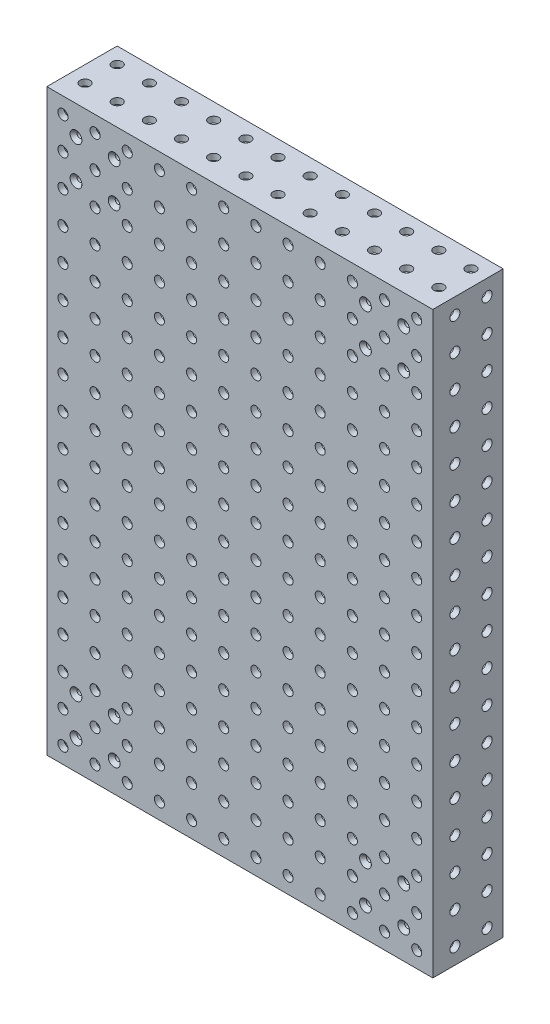
SolidWorks part; units mm, degrees
material "Malleable Cast Iron"
ref_plane "Front Plane" through (0, 0, 0) normal (0, 0, 1) x (1, 0, 0)
ref_plane "Top Plane" through (0, 0, 0) normal (0, 1, 0) x (1, 0, 0)
ref_plane "Right Plane" through (0, 0, 0) normal (1, 0, 0) x (0, 0, -1)
sketch "Sketch1" plane through (0, 0, 0) normal (0, 0, 1) x (1, 0, 0)
  line L0 (25.4, 25.4) -> (25.4, 0) construction
  line L1 (0, 0) -> (609.6, 0)
  line L2 (0, 0) -> (0, 914.4)
  line L3 (0, 914.4) -> (609.6, 914.4)
  line L4 (609.6, 0) -> (609.6, 914.4)
  line L5 (25.4, 0) -> (25.4, 25.4) construction
  line L6 (25.4, 25.4) -> (0, 25.4) construction
  line L7 (584.2, 889) -> (584.2, 914.4) construction
  line L8 (584.2, 889) -> (609.6, 889) construction
  line L9 (46.0375, 868.3625) -> (106.3625, 808.0375) construction
  line L10 (503.2375, 868.3625) -> (563.5625, 808.0375) construction
  line L11 (46.0375, 106.3625) -> (106.3625, 46.0375) construction
  line L12 (503.2375, 106.3625) -> (563.5625, 46.0375) construction
  circle A0 centre (25.4, 25.4) radius 7.9375
  circle A1 centre (76.2, 25.4) radius 7.9375
  circle A2 centre (127, 25.4) radius 7.9375
  circle A3 centre (177.8, 25.4) radius 7.9375
  circle A4 centre (228.6, 25.4) radius 7.9375
  circle A5 centre (279.4, 25.4) radius 7.9375
  circle A6 centre (330.2, 25.4) radius 7.9375
  circle A7 centre (381, 25.4) radius 7.9375
  circle A8 centre (431.8, 25.4) radius 7.9375
  circle A9 centre (482.6, 25.4) radius 7.9375
  circle A10 centre (533.4, 25.4) radius 7.9375
  circle A11 centre (584.2, 25.4) radius 7.9375
  circle A12 centre (76.2, 76.2) radius 7.9375
  circle A13 centre (127, 76.2) radius 7.9375
  circle A14 centre (177.8, 76.2) radius 7.9375
  circle A15 centre (228.6, 76.2) radius 7.9375
  circle A16 centre (279.4, 76.2) radius 7.9375
  circle A17 centre (330.2, 76.2) radius 7.9375
  circle A18 centre (381, 76.2) radius 7.9375
  circle A19 centre (431.8, 76.2) radius 7.9375
  circle A20 centre (482.6, 76.2) radius 7.9375
  circle A21 centre (533.4, 76.2) radius 7.9375
  circle A22 centre (584.2, 76.2) radius 7.9375
  circle A23 centre (76.2, 127) radius 7.9375
  circle A24 centre (127, 127) radius 7.9375
  circle A25 centre (177.8, 127) radius 7.9375
  circle A26 centre (228.6, 127) radius 7.9375
  circle A27 centre (279.4, 127) radius 7.9375
  circle A28 centre (330.2, 127) radius 7.9375
  circle A29 centre (381, 127) radius 7.9375
  circle A30 centre (431.8, 127) radius 7.9375
  circle A31 centre (482.6, 127) radius 7.9375
  circle A32 centre (533.4, 127) radius 7.9375
  circle A33 centre (584.2, 127) radius 7.9375
  circle A34 centre (76.2, 177.8) radius 7.9375
  circle A35 centre (127, 177.8) radius 7.9375
  circle A36 centre (177.8, 177.8) radius 7.9375
  circle A37 centre (228.6, 177.8) radius 7.9375
  circle A38 centre (279.4, 177.8) radius 7.9375
  circle A39 centre (330.2, 177.8) radius 7.9375
  circle A40 centre (381, 177.8) radius 7.9375
  circle A41 centre (431.8, 177.8) radius 7.9375
  circle A42 centre (482.6, 177.8) radius 7.9375
  circle A43 centre (533.4, 177.8) radius 7.9375
  circle A44 centre (584.2, 177.8) radius 7.9375
  circle A45 centre (76.2, 228.6) radius 7.9375
  circle A46 centre (127, 228.6) radius 7.9375
  circle A47 centre (177.8, 228.6) radius 7.9375
  circle A48 centre (228.6, 228.6) radius 7.9375
  circle A49 centre (279.4, 228.6) radius 7.9375
  circle A50 centre (330.2, 228.6) radius 7.9375
  circle A51 centre (381, 228.6) radius 7.9375
  circle A52 centre (431.8, 228.6) radius 7.9375
  circle A53 centre (482.6, 228.6) radius 7.9375
  circle A54 centre (533.4, 228.6) radius 7.9375
  circle A55 centre (584.2, 228.6) radius 7.9375
  circle A56 centre (76.2, 279.4) radius 7.9375
  circle A57 centre (127, 279.4) radius 7.9375
  circle A58 centre (177.8, 279.4) radius 7.9375
  circle A59 centre (228.6, 279.4) radius 7.9375
  circle A60 centre (279.4, 279.4) radius 7.9375
  circle A61 centre (330.2, 279.4) radius 7.9375
  circle A62 centre (381, 279.4) radius 7.9375
  circle A63 centre (431.8, 279.4) radius 7.9375
  circle A64 centre (482.6, 279.4) radius 7.9375
  circle A65 centre (533.4, 279.4) radius 7.9375
  circle A66 centre (584.2, 279.4) radius 7.9375
  circle A67 centre (76.2, 330.2) radius 7.9375
  circle A68 centre (127, 330.2) radius 7.9375
  circle A69 centre (177.8, 330.2) radius 7.9375
  circle A70 centre (228.6, 330.2) radius 7.9375
  circle A71 centre (279.4, 330.2) radius 7.9375
  circle A72 centre (330.2, 330.2) radius 7.9375
  circle A73 centre (381, 330.2) radius 7.9375
  circle A74 centre (431.8, 330.2) radius 7.9375
  circle A75 centre (482.6, 330.2) radius 7.9375
  circle A76 centre (533.4, 330.2) radius 7.9375
  circle A77 centre (584.2, 330.2) radius 7.9375
  circle A78 centre (76.2, 381) radius 7.9375
  circle A79 centre (127, 381) radius 7.9375
  circle A80 centre (177.8, 381) radius 7.9375
  circle A81 centre (228.6, 381) radius 7.9375
  circle A82 centre (279.4, 381) radius 7.9375
  circle A83 centre (330.2, 381) radius 7.9375
  circle A84 centre (381, 381) radius 7.9375
  circle A85 centre (431.8, 381) radius 7.9375
  circle A86 centre (482.6, 381) radius 7.9375
  circle A87 centre (533.4, 381) radius 7.9375
  circle A88 centre (584.2, 381) radius 7.9375
  circle A89 centre (76.2, 431.8) radius 7.9375
  circle A90 centre (127, 431.8) radius 7.9375
  circle A91 centre (177.8, 431.8) radius 7.9375
  circle A92 centre (228.6, 431.8) radius 7.9375
  circle A93 centre (279.4, 431.8) radius 7.9375
  circle A94 centre (330.2, 431.8) radius 7.9375
  circle A95 centre (381, 431.8) radius 7.9375
  circle A96 centre (431.8, 431.8) radius 7.9375
  circle A97 centre (482.6, 431.8) radius 7.9375
  circle A98 centre (533.4, 431.8) radius 7.9375
  circle A99 centre (584.2, 431.8) radius 7.9375
  circle A100 centre (76.2, 482.6) radius 7.9375
  circle A101 centre (127, 482.6) radius 7.9375
  circle A102 centre (177.8, 482.6) radius 7.9375
  circle A103 centre (228.6, 482.6) radius 7.9375
  circle A104 centre (279.4, 482.6) radius 7.9375
  circle A105 centre (330.2, 482.6) radius 7.9375
  circle A106 centre (381, 482.6) radius 7.9375
  circle A107 centre (431.8, 482.6) radius 7.9375
  circle A108 centre (482.6, 482.6) radius 7.9375
  circle A109 centre (533.4, 482.6) radius 7.9375
  circle A110 centre (584.2, 482.6) radius 7.9375
  circle A111 centre (76.2, 533.4) radius 7.9375
  circle A112 centre (127, 533.4) radius 7.9375
  circle A113 centre (177.8, 533.4) radius 7.9375
  circle A114 centre (228.6, 533.4) radius 7.9375
  circle A115 centre (279.4, 533.4) radius 7.9375
  circle A116 centre (330.2, 533.4) radius 7.9375
  circle A117 centre (381, 533.4) radius 7.9375
  circle A118 centre (431.8, 533.4) radius 7.9375
  circle A119 centre (482.6, 533.4) radius 7.9375
  circle A120 centre (533.4, 533.4) radius 7.9375
  circle A121 centre (584.2, 533.4) radius 7.9375
  circle A122 centre (76.2, 584.2) radius 7.9375
  circle A123 centre (127, 584.2) radius 7.9375
  circle A124 centre (177.8, 584.2) radius 7.9375
  circle A125 centre (228.6, 584.2) radius 7.9375
  circle A126 centre (279.4, 584.2) radius 7.9375
  circle A127 centre (330.2, 584.2) radius 7.9375
  circle A128 centre (381, 584.2) radius 7.9375
  circle A129 centre (431.8, 584.2) radius 7.9375
  circle A130 centre (482.6, 584.2) radius 7.9375
  circle A131 centre (533.4, 584.2) radius 7.9375
  circle A132 centre (584.2, 584.2) radius 7.9375
  circle A133 centre (76.2, 635) radius 7.9375
  circle A134 centre (127, 635) radius 7.9375
  circle A135 centre (177.8, 635) radius 7.9375
  circle A136 centre (228.6, 635) radius 7.9375
  circle A137 centre (279.4, 635) radius 7.9375
  circle A138 centre (330.2, 635) radius 7.9375
  circle A139 centre (381, 635) radius 7.9375
  circle A140 centre (431.8, 635) radius 7.9375
  circle A141 centre (482.6, 635) radius 7.9375
  circle A142 centre (533.4, 635) radius 7.9375
  circle A143 centre (584.2, 635) radius 7.9375
  circle A144 centre (76.2, 685.8) radius 7.9375
  circle A145 centre (127, 685.8) radius 7.9375
  circle A146 centre (177.8, 685.8) radius 7.9375
  circle A147 centre (228.6, 685.8) radius 7.9375
  circle A148 centre (279.4, 685.8) radius 7.9375
  circle A149 centre (330.2, 685.8) radius 7.9375
  circle A150 centre (381, 685.8) radius 7.9375
  circle A151 centre (431.8, 685.8) radius 7.9375
  circle A152 centre (482.6, 685.8) radius 7.9375
  circle A153 centre (533.4, 685.8) radius 7.9375
  circle A154 centre (584.2, 685.8) radius 7.9375
  circle A155 centre (76.2, 736.6) radius 7.9375
  circle A156 centre (127, 736.6) radius 7.9375
  circle A157 centre (177.8, 736.6) radius 7.9375
  circle A158 centre (228.6, 736.6) radius 7.9375
  circle A159 centre (279.4, 736.6) radius 7.9375
  circle A160 centre (330.2, 736.6) radius 7.9375
  circle A161 centre (381, 736.6) radius 7.9375
  circle A162 centre (431.8, 736.6) radius 7.9375
  circle A163 centre (482.6, 736.6) radius 7.9375
  circle A164 centre (533.4, 736.6) radius 7.9375
  circle A165 centre (584.2, 736.6) radius 7.9375
  circle A166 centre (76.2, 787.4) radius 7.9375
  circle A167 centre (127, 787.4) radius 7.9375
  circle A168 centre (177.8, 787.4) radius 7.9375
  circle A169 centre (228.6, 787.4) radius 7.9375
  circle A170 centre (279.4, 787.4) radius 7.9375
  circle A171 centre (330.2, 787.4) radius 7.9375
  circle A172 centre (381, 787.4) radius 7.9375
  circle A173 centre (431.8, 787.4) radius 7.9375
  circle A174 centre (482.6, 787.4) radius 7.9375
  circle A175 centre (533.4, 787.4) radius 7.9375
  circle A176 centre (584.2, 787.4) radius 7.9375
  circle A177 centre (76.2, 838.2) radius 7.9375
  circle A178 centre (127, 838.2) radius 7.9375
  circle A179 centre (177.8, 838.2) radius 7.9375
  circle A180 centre (228.6, 838.2) radius 7.9375
  circle A181 centre (279.4, 838.2) radius 7.9375
  circle A182 centre (330.2, 838.2) radius 7.9375
  circle A183 centre (381, 838.2) radius 7.9375
  circle A184 centre (431.8, 838.2) radius 7.9375
  circle A185 centre (482.6, 838.2) radius 7.9375
  circle A186 centre (533.4, 838.2) radius 7.9375
  circle A187 centre (584.2, 838.2) radius 7.9375
  circle A188 centre (76.2, 889) radius 7.9375
  circle A189 centre (127, 889) radius 7.9375
  circle A190 centre (177.8, 889) radius 7.9375
  circle A191 centre (228.6, 889) radius 7.9375
  circle A192 centre (279.4, 889) radius 7.9375
  circle A193 centre (330.2, 889) radius 7.9375
  circle A194 centre (381, 889) radius 7.9375
  circle A195 centre (431.8, 889) radius 7.9375
  circle A196 centre (482.6, 889) radius 7.9375
  circle A197 centre (533.4, 889) radius 7.9375
  circle A198 centre (584.2, 889) radius 7.9375
  circle A199 centre (25.4, 76.2) radius 7.9375
  circle A200 centre (25.4, 127) radius 7.9375
  circle A201 centre (25.4, 177.8) radius 7.9375
  circle A202 centre (25.4, 228.6) radius 7.9375
  circle A203 centre (25.4, 279.4) radius 7.9375
  circle A204 centre (25.4, 330.2) radius 7.9375
  circle A205 centre (25.4, 381) radius 7.9375
  circle A206 centre (25.4, 431.8) radius 7.9375
  circle A207 centre (25.4, 482.6) radius 7.9375
  circle A208 centre (25.4, 533.4) radius 7.9375
  circle A209 centre (25.4, 584.2) radius 7.9375
  circle A210 centre (25.4, 635) radius 7.9375
  circle A211 centre (25.4, 685.8) radius 7.9375
  circle A212 centre (25.4, 736.6) radius 7.9375
  circle A213 centre (25.4, 787.4) radius 7.9375
  circle A214 centre (25.4, 838.2) radius 7.9375
  circle A215 centre (25.4, 889) radius 7.9375
  circle A216 centre (46.0375, 868.3625) radius 4.2333
  circle A217 centre (106.3625, 868.3625) radius 4.2333
  circle A218 centre (46.0375, 808.0375) radius 4.2333
  circle A219 centre (106.3625, 808.0375) radius 4.2333
  circle A220 centre (503.2375, 868.3625) radius 4.2333
  circle A221 centre (563.5625, 868.3625) radius 4.2333
  circle A222 centre (503.2375, 808.0375) radius 4.2333
  circle A223 centre (563.5625, 808.0375) radius 4.2333
  circle A224 centre (46.0375, 106.3625) radius 4.2333
  circle A225 centre (106.3625, 106.3625) radius 4.2333
  circle A226 centre (46.0375, 46.0375) radius 4.2333
  circle A227 centre (106.3625, 46.0375) radius 4.2333
  circle A228 centre (503.2375, 106.3625) radius 4.2333
  circle A229 centre (563.5625, 106.3625) radius 4.2333
  circle A230 centre (503.2375, 46.0375) radius 4.2333
  circle A231 centre (563.5625, 46.0375) radius 4.2333
  point P449 (76.2, 838.2)
  point P459 (533.4, 838.2)
  point P469 (76.2, 76.2)
  point P479 (533.4, 76.2)
  dimension "D3" = 15.875
  dimension "D8" = 8.4666
  dimension "D1" = 609.6
  dimension "D2" = 914.4
  dimension "D6" = 60.325
  dimension "D7" = 60.325
  dimension "D4" = 12
  dimension "D5" = 18
extrude "Boss-Extrude1" add sketch "Sketch1" along normal blind 9.525
sketch "Sketch2" plane through (0, 0, 9.525) normal (0, 0, 1) x (1, 0, 0)
  line L0 (9.525, 9.525) -> (9.525, 904.875)
  line L1 (0, 0) -> (609.6, 0)
  line L2 (0, 0) -> (0, 914.4)
  line L3 (0, 914.4) -> (609.6, 914.4)
  line L4 (609.6, 0) -> (609.6, 914.4)
  line L5 (9.525, 904.875) -> (600.075, 904.875)
  line L6 (600.075, 9.525) -> (600.075, 904.875)
  line L7 (9.525, 9.525) -> (600.075, 9.525)
  dimension "D1" = 9.525
extrude "Boss-Extrude2" add sketch "Sketch2" against normal blind 111.125
sketch "Sketch3" plane through (0, 0, 0) normal (0, -1, 0) x (1, 0, 0)
  line L1 (0, -101.6) -> (609.6, -101.6) construction
  line L2 (25.4, -25.4) -> (0, -25.4) construction
  line L3 (0, 9.525) -> (0, -101.6) construction
  line L4 (584.2, -25.4) -> (609.6, -25.4) construction
  line L5 (609.6, 9.525) -> (609.6, -101.6) construction
  circle A0 centre (25.4, -25.4) radius 7.9375
  circle A1 centre (76.2, -25.4) radius 7.9375
  circle A2 centre (127, -25.4) radius 7.9375
  circle A3 centre (177.8, -25.4) radius 7.9375
  circle A4 centre (228.6, -25.4) radius 7.9375
  circle A5 centre (279.4, -25.4) radius 7.9375
  circle A6 centre (330.2, -25.4) radius 7.9375
  circle A7 centre (381, -25.4) radius 7.9375
  circle A8 centre (431.8, -25.4) radius 7.9375
  circle A9 centre (482.6, -25.4) radius 7.9375
  circle A10 centre (533.4, -25.4) radius 7.9375
  circle A11 centre (584.2, -25.4) radius 7.9375
  circle A12 centre (76.2, -76.2) radius 7.9375
  circle A13 centre (127, -76.2) radius 7.9375
  circle A14 centre (177.8, -76.2) radius 7.9375
  circle A15 centre (228.6, -76.2) radius 7.9375
  circle A16 centre (279.4, -76.2) radius 7.9375
  circle A17 centre (330.2, -76.2) radius 7.9375
  circle A18 centre (381, -76.2) radius 7.9375
  circle A19 centre (431.8, -76.2) radius 7.9375
  circle A20 centre (482.6, -76.2) radius 7.9375
  circle A21 centre (533.4, -76.2) radius 7.9375
  circle A22 centre (584.2, -76.2) radius 7.9375
  circle A23 centre (25.4, -76.2) radius 7.9375
  dimension "D1" = 15.875
  dimension "D4" = 25.4
  dimension "D2" = 12
  dimension "D3" = 2
extrude "Cut-Extrude1" cut sketch "Sketch3" against normal through all
sketch "Sketch4" plane through (609.6, 0, 0) normal (1, 0, 0) x (0, 0, -1)
  line L0 (101.6, 0) -> (101.6, 914.4) construction
  line L1 (25.4, 25.4) -> (25.4, 0) construction
  line L2 (-9.525, 0) -> (101.6, 0) construction
  line L3 (25.4, 889) -> (25.4, 914.4) construction
  line L4 (-9.525, 914.4) -> (101.6, 914.4) construction
  circle A0 centre (25.4, 25.4) radius 7.9375
  circle A1 centre (76.2, 25.4) radius 7.9375
  circle A2 centre (76.2, 76.2) radius 7.9375
  circle A3 centre (76.2, 127) radius 7.9375
  circle A4 centre (76.2, 177.8) radius 7.9375
  circle A5 centre (76.2, 228.6) radius 7.9375
  circle A6 centre (76.2, 279.4) radius 7.9375
  circle A7 centre (76.2, 330.2) radius 7.9375
  circle A8 centre (76.2, 381) radius 7.9375
  circle A9 centre (76.2, 431.8) radius 7.9375
  circle A10 centre (76.2, 482.6) radius 7.9375
  circle A11 centre (76.2, 533.4) radius 7.9375
  circle A12 centre (76.2, 584.2) radius 7.9375
  circle A13 centre (76.2, 635) radius 7.9375
  circle A14 centre (76.2, 685.8) radius 7.9375
  circle A15 centre (76.2, 736.6) radius 7.9375
  circle A16 centre (76.2, 787.4) radius 7.9375
  circle A17 centre (76.2, 838.2) radius 7.9375
  circle A18 centre (76.2, 889) radius 7.9375
  circle A19 centre (25.4, 76.2) radius 7.9375
  circle A20 centre (25.4, 127) radius 7.9375
  circle A21 centre (25.4, 177.8) radius 7.9375
  circle A22 centre (25.4, 228.6) radius 7.9375
  circle A23 centre (25.4, 279.4) radius 7.9375
  circle A24 centre (25.4, 330.2) radius 7.9375
  circle A25 centre (25.4, 381) radius 7.9375
  circle A26 centre (25.4, 431.8) radius 7.9375
  circle A27 centre (25.4, 482.6) radius 7.9375
  circle A28 centre (25.4, 533.4) radius 7.9375
  circle A29 centre (25.4, 584.2) radius 7.9375
  circle A30 centre (25.4, 635) radius 7.9375
  circle A31 centre (25.4, 685.8) radius 7.9375
  circle A32 centre (25.4, 736.6) radius 7.9375
  circle A33 centre (25.4, 787.4) radius 7.9375
  circle A34 centre (25.4, 838.2) radius 7.9375
  circle A35 centre (25.4, 889) radius 7.9375
  dimension "D1" = 15.875
  dimension "D4" = 25.4
  dimension "D2" = 2
  dimension "D3" = 18
extrude "Cut-Extrude2" cut sketch "Sketch4" against normal through all
chamfer "Chamfer1" distance 5.08 angle 49 16 edges at (50.2708, 46.0375, 9.525) (50.2708, 808.0375, 9.525) (110.5958, 808.0375, 9.525) (110.5958, 868.3625, 9.525) (50.2708, 868.3625, 9.525) (567.7958, 808.0375, 9.525) (507.4708, 808.0375, 9.525) (507.4708, 868.3625, 9.525) (567.7958, 868.3625, 9.525) (567.7958, 46.0375, 9.525) (567.7958, 106.3625, 9.525) (507.4708, 106.3625, 9.525) (507.4708, 46.0375, 9.525) (110.5958, 46.0375, 9.525) (110.5958, 106.3625, 9.525) (50.2708, 106.3625, 9.525) first distance on face at (304.8, 457.2, 9.525)
